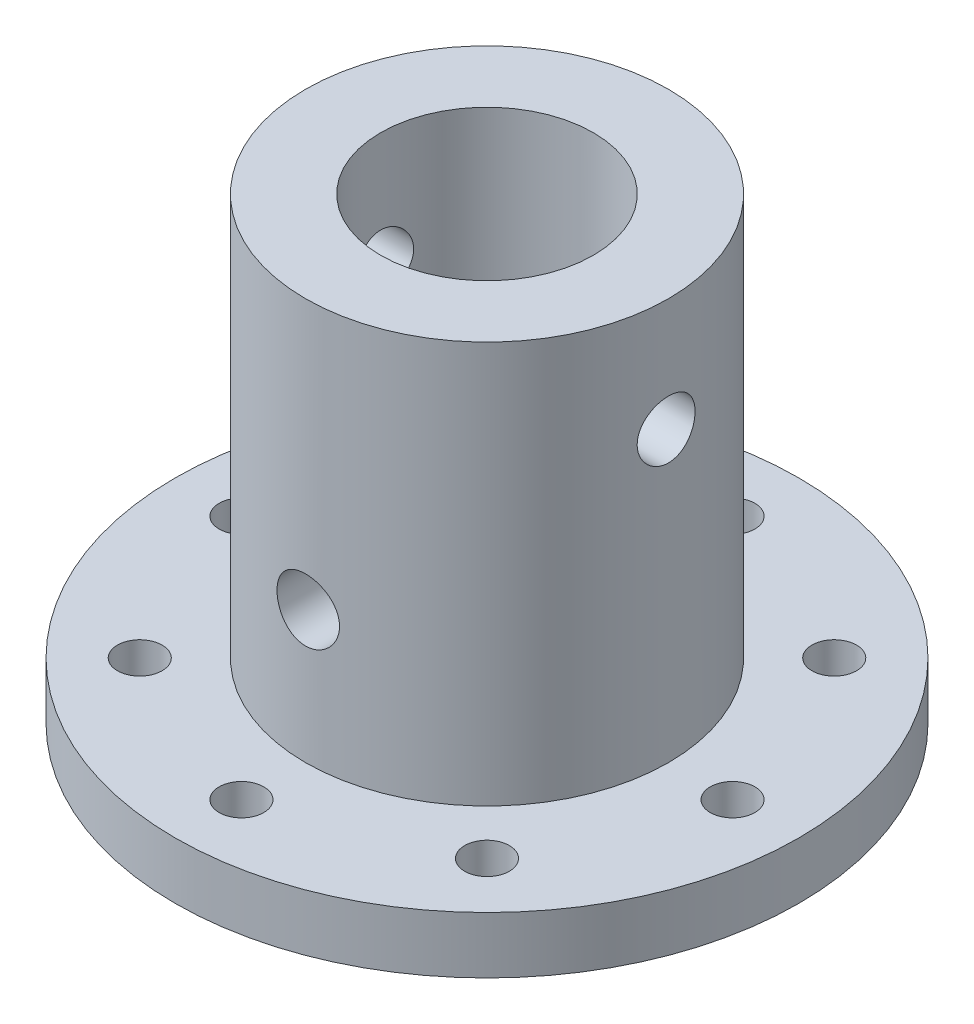
SolidWorks part; units mm, degrees
ref_plane "Front Plane" through (0, 0, 0) normal (0, 0, 1) x (1, 0, 0)
ref_plane "Top Plane" through (0, 0, 0) normal (0, 1, 0) x (1, 0, 0)
ref_plane "Right Plane" through (0, 0, 0) normal (1, 0, 0) x (0, 0, -1)
sketch "Sketch1" plane through (0, 0, 0) normal (0, 1, 0) x (1, 0, 0)
  circle A0 centre (0, 0) radius 13.97
extrude "Boss-Extrude1" add sketch "Sketch1" along normal blind 2.54
sketch "Sketch2" plane through (0, 2.54, 0) normal (0, 1, 0) x (1, 0, 0)
  circle A0 centre (0, 0) radius 8.128
extrude "Boss-Extrude2" add sketch "Sketch2" along normal blind 18
sketch "Sketch4" plane through (0, 20.54, 0) normal (0, 1, 0) x (1, 0, 0)
  circle A0 centre (0, 0) radius 8.128
sketch "Sketch6" plane through (0, 0, 0) normal (0, -1, 0) x (-1, 0, 0)
  circle A1 centre (-11, 0) radius 1
  circle A2 centre (-7.7782, 7.7782) radius 1
  circle A3 centre (0, 11) radius 1
  circle A4 centre (7.7782, 7.7782) radius 1
  circle A5 centre (11, 0) radius 1
  circle A6 centre (7.7782, -7.7782) radius 1
  circle A7 centre (0, -11) radius 1
  circle A8 centre (-7.7782, -7.7782) radius 1
  point P22 (0, 0)
  dimension "D1" = 8
  dimension "D2" = 11
extrude "Cut-Extrude2" cut sketch "Sketch6" against normal through all
sketch "Sketch7" plane through (0, 20.54, 0) normal (0, 1, 0) x (1, 0, 0)
  circle A0 centre (0, 0) radius 4.7625
extrude "Cut-Extrude3" cut sketch "Sketch7" against normal blind 25.4
sketch "Sketch11" plane through (0, 0, 0) normal (0, 0, 1) x (1, 0, 0)
  line L0 (8.128, 20.54) -> (-8.128, 20.54) construction
  circle A0 centre (0, 8.466) radius 1.4
  dimension "D1" = 12.074
extrude "Cut-Extrude6" cut sketch "Sketch11" against normal blind 24.13 and the other way blind 24.13
sketch "Sketch12" plane through (0, 0, 0) normal (1, 0, 0) x (0, 0, -1)
  line L0 (8.128, 20.54) -> (-8.128, 20.54) construction
  circle A0 centre (0, 15.466) radius 1.2966
  dimension "D1" = 5.074
extrude "Cut-Extrude7" cut sketch "Sketch12" against normal through all and the other way through all
